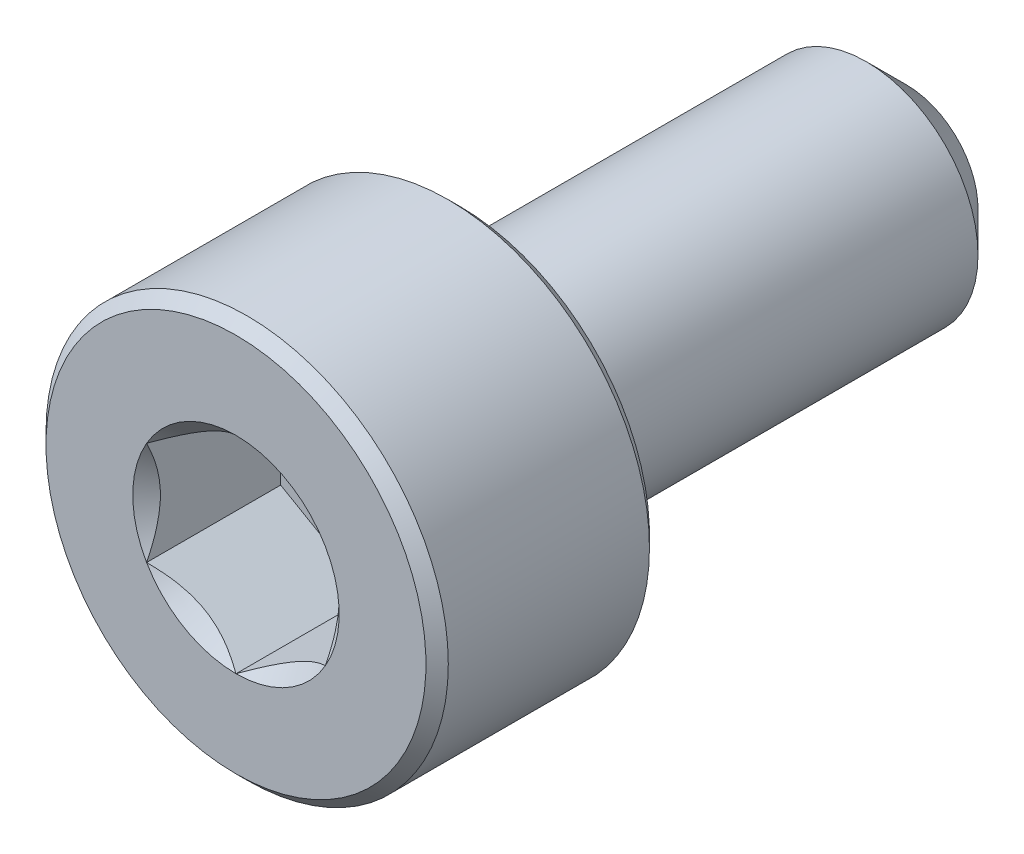
SolidWorks part; units mm, degrees
material "Alloy Steel"
ref_plane "Front Plane" through (0, 0, 0) normal (0, 0, 1) x (1, 0, 0)
ref_plane "Top Plane" through (0, 0, 0) normal (0, 1, 0) x (1, 0, 0)
ref_plane "Right Plane" through (0, 0, 0) normal (1, 0, 0) x (0, 0, -1)
sketch "Sketch1" plane through (0, 0, 0) normal (1, 0, 0) x (0, 0, -1)
  line L0 (-3.75, 0) -> (3.75, 0) construction
  line L1 (3.75, 0) -> (3.75, 0.8) construction
  line L2 (3.75, 0.8) -> (3.3, 1.25) construction
  line L3 (3.3, 1.25) -> (3.4125, 1.25) construction
  line L4 (3.4125, 1.25) -> (-1.25, 1.25) construction
  line L5 (-1.25, 1.25) -> (-1.25, 2.25) construction
  line L6 (-1.25, 2.25) -> (-3.75, 2.25) construction
  line L7 (-3.75, 2.25) -> (-3.75, 0) construction
  line L8 (3.75, 0.8) -> (3.75, 1.25) construction
  line L9 (3.7219, 1.2987) -> (3.9469, 0.909) construction
  line L10 (3.9469, 0.909) -> (4.1719, 1.2987) construction
  line L11 (4.1719, 1.2987) -> (3.7219, 1.2987) construction
  line L12 (3.9469, 1.2987) -> (3.9469, 1.25) construction
  line L13 (3.9469, 0.909) -> (3.9469, 0.9577) construction
  line L14 (3.9187, 0.9577) -> (3.975, 0.9577) construction
  line L15 (3.75, 1.25) -> (4.1437, 1.25) construction
  line L16 (3.7359, 1.2744) -> (4.1578, 1.2744) construction
  line L17 (3.75, 0) -> (3.75, -1.25) construction
  line L18 (-1.375, 2.25) -> (-1.25, 2.125) construction
  line L19 (-3.625, 2.25) -> (-3.75, 2.125) construction
  line L20 (-1.25, 1.25) -> (-1.25, 0) construction
  line L21 (-1.25, 0.625) -> (0.4167, 0.625) construction
  line L22 (0.4167, 0.625) -> (2.0833, 0.625) construction
  line L23 (2.0833, 0.625) -> (3.75, 0.625) construction
  line L24 (0.4167, 0.625) -> (0.4167, 1.25) construction
  line L25 (0.4167, 1.25) -> (0.4167, 2.25) construction
  line L26 (2.0833, 0.625) -> (2.0833, 2.25) construction
  point P0 (-3.75, 1)
  point P3 (2.625, 1.25)
  point P4 (0, 0)
  point P18 (2.0833, 1.25)
  point P22 (3.9469, 0.9577)
  point P24 (3.4125, 1.25)
  point P25 (3.9469, 1.25)
  point P28 (3.9469, 1.2744)
  point P29 (2.625, -1.25)
  point P30 (0.4167, 1.25)
  point P31 (-2.5, 2.25)
  point P37 (-1.6875, 2.25)
  point P38 (-3.5625, 2.25)
  point P45 (0.4167, 0.625)
  point P46 (2.0833, 0.625)
  dimension "D1" = 45
  dimension "D2" = 0.0563
  dimension "D3" = 0.45
  dimension "D7" = 0.125
  dimension "D8" = 0.125
  dimension "D9" = 0.125
  dimension "D10" = 0.0625
  dimension "D11" = 0.3125
  dimension "Drive Size" = 2
  dimension "Head Diameter" = 4.5
  dimension "Head Height" = 2.5
  dimension "Thread Pitch" = 0.45
  dimension "Thread Major Diameter" = 2.5
  dimension "Length" = 5
  dimension "D12" = 0.3375
  dimension "D4" = 1.125
sketch "Sketch2" plane through (0, 0, 0) normal (1, 0, 0) x (0, 0, -1)
  line L0 (-3.75, 0) -> (-3.75, 2.125)
  line L1 (-3.625, 2.25) -> (-1.375, 2.25)
  line L2 (-1.25, 2.125) -> (-1.25, 1.25)
  line L3 (-1.25, 1.25) -> (3.3, 1.25)
  line L4 (3.3, 1.25) -> (3.75, 0.8)
  line L5 (3.75, 0.8) -> (3.75, 0)
  line L6 (-1.375, 2.25) -> (-1.25, 2.125) construction
  line L7 (3.75, 0) -> (-3.75, 0)
  line L8 (-3.625, 2.25) -> (-3.75, 2.125) construction
  line L9 (-1.375, 2.25) -> (-1.25, 2.125)
  line L10 (-3.625, 2.25) -> (-3.75, 2.125)
revolve "Revolve1" add sketch "Sketch2" angle 360 about L7
sketch "Sketch3" plane through (0, 0, 3.75) normal (0, 0, 1) x (1, 0, 0)
  line L1 (1, -0.5774) -> (1, 0.5774)
  line L2 (1, 0.5774) -> (0, 1.1547)
  line L3 (0, 1.1547) -> (-1, 0.5774)
  line L4 (-1, 0.5774) -> (-1, -0.5774)
  line L5 (-1, -0.5774) -> (0, -1.1547)
  line L6 (0, -1.1547) -> (1, -0.5774)
  circle A0 centre (0, 0) radius 1 construction
extrude "Cut-Extrude1" cut sketch "Sketch3" against normal offset from surface (1.5 mm away) 1 up to face at (0, 2.125, 1.25)
sketch "Sketch4" plane through (0, 0, 3.75) normal (0, 0, 1) x (1, 0, 0)
  circle A0 centre (0, 0) radius 1.1547
extrude "Cut-Extrude2" cut sketch "Sketch4" against normal up to vertex (1.25 mm away) draft 45 up to point (0, 2.25, 2.5)
ref_plane "Plane1" [suppressed] through (0, 0, -3.4125) normal (0, 0, 1) x (1, 0, 0)
split "Split1" [suppressed] bodies to split 106
sketch "Sketch6" [suppressed] plane through (0, 0, -3.75) normal (0, 0, -1) x (-1, 0, 0)
  circle A0 centre (0, 0) radius 1.25
curve "Helix/Spiral1" [suppressed] pitch 0.45 height 5.5175 turns 12.2611
sketch "Sketch7" [suppressed] plane through (0, 0, 0) normal (1, 0, 0) x (0, 0, -1)
  line L0 (3.7359, 1.2744) -> (4.1578, 1.2744)
  line L1 (4.1578, 1.2744) -> (3.975, 0.9577)
  line L2 (3.975, 0.9577) -> (3.9187, 0.9577)
  line L3 (3.9187, 0.9577) -> (3.7359, 1.2744)
sweep "Cut-Sweep1" [suppressed] cut profiles "Sketch7" path "Helix/Spiral1"
sketch "Sketch8" [suppressed] plane through (0, 0, 1.25) normal (0, 0, -1) x (-1, 0, 0)
  circle A0 centre (0, 0) radius 1.25
extrude "Boss-Extrude1" [suppressed] add sketch "Sketch8" along normal through all draft 45
equation "\"D2@Sketch1\" = \"Thread Pitch@Sketch1\" / 8"
equation "\"D3@Sketch1\"= \"Thread Pitch@Sketch1\""
equation "\"D4@Helix/Spiral1\" = \"Thread Pitch@Sketch1\""
equation "\"D7@Sketch1\" = \"Head Height@Sketch1\" * .05"
equation "\"D8@Sketch1\"=\"D7@Sketch1\""
equation "\"D9@Sketch1\"=\"D7@Sketch1\""
equation "\"D10@Sketch1\"=\"D7@Sketch1\"/2"
equation "\"D11@Sketch1\"=\"D10@Sketch1\"*5"
equation "\"D4@Sketch1\"=\"Thread Pitch@Sketch1\"*2.5"
equation "\"D12@Sketch1\"=\"Thread Pitch@Sketch1\"*.75"
